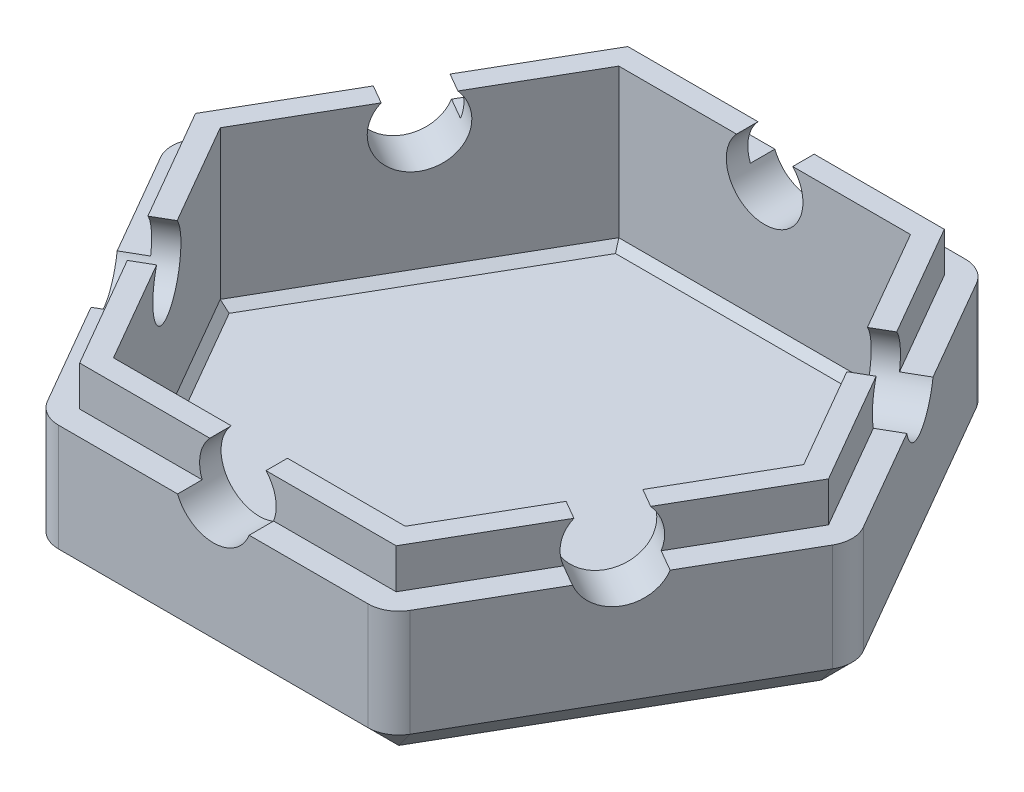
SolidWorks part; units mm, degrees
ref_plane "Front Plane" through (0, 0, 0) normal (0, 0, 1) x (1, 0, 0)
ref_plane "Top Plane" through (0, 0, 0) normal (0, 1, 0) x (1, 0, 0)
ref_plane "Right Plane" through (0, 0, 0) normal (1, 0, 0) x (0, 0, -1)
sketch "Sketch1" plane through (0, 0, 0) normal (0, 1, 0) x (1, 0, 0)
  line L0 (22.5, 0) -> (0, 0) construction
  line L1 (22.5, 0) -> (11.25, 19.4856)
  line L2 (11.25, 19.4856) -> (-11.25, 19.4856)
  line L3 (-11.25, 19.4856) -> (-22.5, 0)
  line L4 (-22.5, 0) -> (-11.25, -19.4856)
  line L5 (-11.25, -19.4856) -> (11.25, -19.4856)
  line L6 (11.25, -19.4856) -> (22.5, 0)
  circle A0 centre (0, 0) radius 19.4856 construction
  dimension "D1" = 22.5
extrude "Boss-Extrude1" add sketch "Sketch1" against normal blind 10 from offset 3.7 offset against normal yes
sketch "Sketch2" plane through (0, -3.7, 0) normal (0, 1, 0) x (1, 0, 0)
  line L0 (19.0359, 0) -> (9.5179, 16.4856)
  line L1 (9.5179, 16.4856) -> (-9.5179, 16.4856)
  line L2 (-9.5179, 16.4856) -> (-19.0359, 0)
  line L3 (-19.0359, 0) -> (-9.5179, -16.4856)
  line L4 (-9.5179, -16.4856) -> (9.5179, -16.4856)
  line L5 (9.5179, -16.4856) -> (19.0359, 0)
  line L6 (11.25, -19.4856) -> (22.5, 0)
  line L7 (22.5, 0) -> (11.25, 19.4856)
  line L8 (11.25, 19.4856) -> (-11.25, 19.4856)
  line L9 (-11.25, 19.4856) -> (-22.5, 0)
  line L10 (-22.5, 0) -> (-11.25, -19.4856)
  line L11 (-11.25, -19.4856) -> (11.25, -19.4856)
  line L12 (11.25, -19.4856) -> (22.5, 0)
  line L13 (22.5, 0) -> (11.25, 19.4856)
  line L14 (11.25, 19.4856) -> (-11.25, 19.4856)
  line L15 (-11.25, 19.4856) -> (-22.5, 0)
  line L16 (-22.5, 0) -> (-11.25, -19.4856)
  line L17 (-11.25, -19.4856) -> (11.25, -19.4856)
  dimension "D1" = 0
  dimension "D2" = 3
extrude "Cut-Extrude1" cut sketch "Sketch2" against normal blind 8.6 contours L4 L5 L0 L1 L2 L3 region at (0, -3.7, 0)
sketch "Sketch3" plane through (0, -3.7, 0) normal (0, 1, 0) x (1, 0, 0)
  line L0 (10.3262, -17.8856) -> (20.6525, 0)
  line L1 (20.6525, 0) -> (10.3262, 17.8856)
  line L2 (10.3262, 17.8856) -> (-10.3262, 17.8856)
  line L3 (-10.3262, 17.8856) -> (-20.6525, 0)
  line L4 (-20.6525, 0) -> (-10.3262, -17.8856)
  line L5 (-10.3262, -17.8856) -> (10.3262, -17.8856)
  line L6 (-9.5179, -16.4856) -> (9.5179, -16.4856)
  line L7 (-19.0359, 0) -> (-9.5179, -16.4856)
  line L8 (-9.5179, 16.4856) -> (-19.0359, 0)
  line L9 (9.5179, 16.4856) -> (-9.5179, 16.4856)
  line L10 (19.0359, 0) -> (9.5179, 16.4856)
  line L11 (9.5179, -16.4856) -> (19.0359, 0)
  line L12 (-9.5179, -16.4856) -> (9.5179, -16.4856)
  line L13 (-19.0359, 0) -> (-9.5179, -16.4856)
  line L14 (-9.5179, 16.4856) -> (-19.0359, 0)
  line L15 (9.5179, 16.4856) -> (-9.5179, 16.4856)
  line L16 (19.0359, 0) -> (9.5179, 16.4856)
  line L17 (9.5179, -16.4856) -> (19.0359, 0)
  dimension "D1" = 0
  dimension "D2" = 1.4
extrude "Boss-Extrude2" add sketch "Sketch3" along normal blind 1.6
fillet "Fillet1" radius 2 6 edges at (22.5, -8.7, 0) (11.25, -8.7, 19.4856) (-11.25, -8.7, 19.4856) (-22.5, -8.7, 0) (-11.25, -8.7, -19.4856) (11.25, -8.7, -19.4856)
sketch "Sketch6" plane through (0, -3.7, 0) normal (0, 1, 0) x (1, 0, 0)
  line L6 (10.3262, -17.8856) -> (20.6525, 0)
  line L7 (-10.3262, -17.8856) -> (10.3262, -17.8856)
  line L8 (-20.6525, 0) -> (-10.3262, -17.8856)
  line L9 (-10.3262, 17.8856) -> (-20.6525, 0)
  line L10 (10.3262, 17.8856) -> (-10.3262, 17.8856)
  line L11 (20.6525, 0) -> (10.3262, 17.8856)
  line L12 (10.3262, -17.8856) -> (20.6525, 0)
  line L13 (-10.3262, -17.8856) -> (10.3262, -17.8856)
  line L14 (-20.6525, 0) -> (-10.3262, -17.8856)
  line L15 (-10.3262, 17.8856) -> (-20.6525, 0)
  line L16 (10.3262, 17.8856) -> (-10.3262, 17.8856)
  line L17 (20.6525, 0) -> (10.3262, 17.8856)
  line L18 (11.8274, -18.4856) -> (21.9226, -1)
  line L19 (21.9226, 1) -> (11.8274, 18.4856)
  line L20 (10.0953, 19.4856) -> (-10.0953, 19.4856)
  line L21 (-11.8274, 18.4856) -> (-21.9226, 1)
  line L22 (-21.9226, -1) -> (-11.8274, -18.4856)
  line L23 (-10.0953, -19.4856) -> (10.0953, -19.4856)
  line L24 (11.8274, -18.4856) -> (21.9226, -1)
  line L25 (21.9226, 1) -> (11.8274, 18.4856)
  line L26 (10.0953, 19.4856) -> (-10.0953, 19.4856)
  line L27 (-11.8274, 18.4856) -> (-21.9226, 1)
  line L28 (-21.9226, -1) -> (-11.8274, -18.4856)
  line L29 (-10.0953, -19.4856) -> (10.0953, -19.4856)
  arc A6 (21.9226, -1) -> (21.9226, 1) centre (20.1906, 0) ccw
  arc A7 (11.8274, 18.4856) -> (10.0953, 19.4856) centre (10.0953, 17.4856) ccw
  arc A8 (-10.0953, 19.4856) -> (-11.8274, 18.4856) centre (-10.0953, 17.4856) ccw
  arc A9 (-21.9226, 1) -> (-21.9226, -1) centre (-20.1906, 0) ccw
  arc A10 (-11.8274, -18.4856) -> (-10.0953, -19.4856) centre (-10.0953, -17.4856) ccw
  arc A11 (10.0953, -19.4856) -> (11.8274, -18.4856) centre (10.0953, -17.4856) ccw
  arc A12 (21.9226, -1) -> (21.9226, 1) centre (20.1906, 0) ccw
  arc A13 (11.8274, 18.4856) -> (10.0953, 19.4856) centre (10.0953, 17.4856) ccw
  arc A14 (-10.0953, 19.4856) -> (-11.8274, 18.4856) centre (-10.0953, 17.4856) ccw
  arc A15 (-21.9226, 1) -> (-21.9226, -1) centre (-20.1906, 0) ccw
  arc A16 (-11.8274, -18.4856) -> (-10.0953, -19.4856) centre (-10.0953, -17.4856) ccw
  arc A17 (10.0953, -19.4856) -> (11.8274, -18.4856) centre (10.0953, -17.4856) ccw
  dimension "D1" = 0
  dimension "D2" = 0
extrude "Cut-Extrude4" cut sketch "Sketch6" against normal blind 1
sketch "Sketch4" plane through (0, 0, -19.4856) normal (0, 0, -1) x (-1, 0, 0)
  line L0 (0, -3.7) -> (0, -3.8) construction
  line L2 (0, -3.7) -> (0, 0) construction
  circle A0 centre (0, -3.8) radius 2.5
  dimension "D2" = 5
  dimension "D1" = 0.1
  dimension "D3" = 3.7
extrude "Cut-Extrude3" cut sketch "Sketch4" against normal up to next
ref_axis "Axis1" through (0, -12.18, 0) along (0, 1, 0)
pattern_circular "CirPattern1" count 6 every 60 about axis through (0, -12.18, 0) along (0, 1, 0) of "Cut-Extrude3"
chamfer "Chamfer1" distance 0.5 angle 45 6 edges at (-14.2769, -12.3, 8.2428) (-14.2769, -12.3, -8.2428) (0, -12.3, -16.4856) (14.2769, -12.3, -8.2428) (14.2769, -12.3, 8.2428) (0, -12.3, 16.4856)
chamfer "Chamfer2" distance 2 angle 45 12 edges at (0, -13.7, 19.4856) (11.0953, -13.7, 19.2176) (-11.0953, -13.7, 19.2176) (16.875, -13.7, 9.7428) (-16.875, -13.7, 9.7428) (22.1906, -13.7, 0) (-22.1906, -13.7, 0) (16.875, -13.7, -9.7428) (-16.875, -13.7, -9.7428) (11.0953, -13.7, -19.2176) (-11.0953, -13.7, -19.2176) (0, -13.7, -19.4856)
